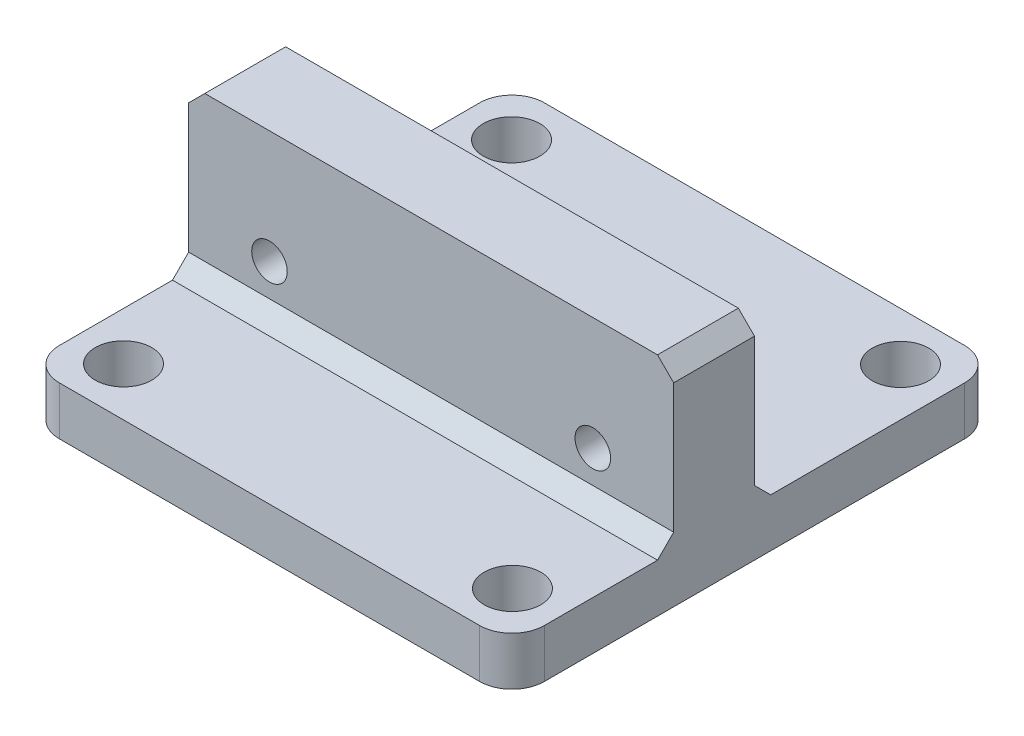
SolidWorks part; units mm, degrees
material "6061-T6 (SS)"
ref_plane "Front Plane" through (0, 0, 0) normal (0, 0, 1) x (1, 0, 0)
ref_plane "Top Plane" through (0, 0, 0) normal (0, 1, 0) x (1, 0, 0)
ref_plane "Right Plane" through (0, 0, 0) normal (1, 0, 0) x (0, 0, -1)
sketch "Sketch1" plane through (0, 0, 0) normal (1, 0, 0) x (0, 0, -1)
  line L0 (-15, 0) -> (15, 0)
  line L1 (15, 0) -> (15, 3)
  line L2 (15, 3) -> (0, 3)
  line L3 (0, 3) -> (0, 13)
  line L4 (0, 13) -> (-5, 13)
  line L5 (-5, 13) -> (-5, 3)
  line L6 (-5, 3) -> (-15, 3)
  line L7 (-15, 3) -> (-15, 0)
  point P4 (0, 0)
  dimension "D1" = 30
  dimension "D2" = 3
  dimension "D3" = 15
  dimension "D4" = 5
  dimension "D5" = 10
extrude "Boss-Extrude1" add sketch "Sketch1" along normal mid plane 30
hole_wizard "Ø3.5 (3.5) Diameter Hole1" positions "Sketch4" profile "Sketch5" hole size "Ø3.5" standard "ISO" end condition through all
sketch "Sketch4" plane through (0, 3, 0) normal (0, 1, 0) x (1, 0, 0)
  line L0 (0, 0) -> (15, 0) construction
  line L2 (0, 0) -> (0, 15) construction
  line L3 (15, 15) -> (-15, 15) construction
  point P0 (-12.0295, 12)
  point P16 (12.0295, 12)
  point P17 (0, 0)
  point P18 (-12.0295, -12)
  point P19 (12.0295, -12)
  point P24 (4.9859, 0)
  dimension "D1" = 12.0295
  dimension "D2" = 12
sketch "Sketch5" plane through (-12.0295, 3, -12) normal (1, 0, 0) x (0, 0, 1)
  line L0 (0, 0) -> (0, 3)
  line L1 (0, 3) -> (1.75, 3)
  line L2 (1.75, 3) -> (1.75, 0)
  line L5 (1.75, 0) -> (0, 0)
  line L11 (0, -6.35) -> (0, 107.95) construction
  dimension "Thru Hole Dia." = 3.5
  dimension "Thru Hole Depth" = 3
fillet "Fillet1" radius 2 4 edges at (-15, 1.5, 15) (15, 1.5, 15) (-15, 1.5, -15) (15, 1.5, -15)
hole_wizard "Ø2.2 (2.2) Diameter Hole1" positions "Sketch6" profile "Sketch7" hole size "Ø2.2" standard "ISO" end condition through all
sketch "Sketch6" plane through (0, 0, 0) normal (0, 0, -1) x (-1, 0, 0)
  line L1 (-13, 3) -> (13, 3) construction
  point P0 (-10, 6)
  point P2 (10, 6)
  point P6 (0, 0)
  point P11 (0, 0)
  dimension "D1" = 20
  dimension "D2" = 10
  dimension "D3" = 3
sketch "Sketch7" plane through (10, 6, 0) normal (1, 0, 0) x (0, 1, 0)
  line L0 (0, 0) -> (0, 15)
  line L1 (0, 15) -> (1.1, 15)
  line L2 (1.1, 15) -> (1.1, 0)
  line L5 (1.1, 0) -> (0, 0)
  line L11 (0, -6.35) -> (0, 107.95) construction
  dimension "Thru Hole Dia." = 2.2
  dimension "Thru Hole Depth" = 15
chamfer "Chamfer1" distance 1 angle 45 2 edges at (0, 3, 0) (0, 3, 5)
chamfer "Chamfer2" distance 1 angle 45 2 edges at (-15, 13, 2.5) (15, 13, 2.5)
equation "\"D2@Sketch6\"=\"D1@Sketch6\"/2"
